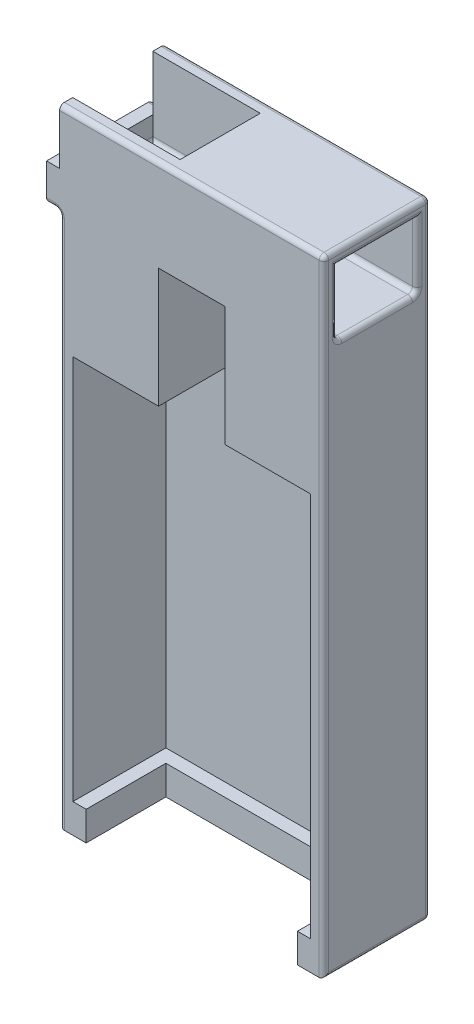
SolidWorks part; units mm, degrees
ref_plane "Front Plane" through (0, 0, 0) normal (0, 0, 1) x (1, 0, 0)
ref_plane "Top Plane" through (0, 0, 0) normal (0, 1, 0) x (1, 0, 0)
ref_plane "Right Plane" through (0, 0, 0) normal (1, 0, 0) x (0, 0, -1)
sketch "Sketch1" plane through (0, 0, 0) normal (0, 1, 0) x (1, 0, 0)
  line L0 (-22.733, -7.62) -> (-22.733, -10.16)
  line L1 (-25.273, -10.16) -> (25.273, -10.16)
  line L2 (-25.273, -10.16) -> (-25.273, 10.16)
  line L3 (-25.273, 10.16) -> (25.273, 10.16)
  line L4 (25.273, -10.16) -> (25.273, 10.16)
  line L5 (-25.273, -10.16) -> (25.273, 10.16) construction
  line L6 (-25.273, 10.16) -> (25.273, -10.16) construction
  line L7 (-22.733, -7.62) -> (22.733, -7.62)
  line L8 (-22.733, -7.62) -> (-22.733, 7.62)
  line L9 (-22.733, 7.62) -> (22.733, 7.62)
  line L10 (22.733, -7.62) -> (22.733, 7.62)
  line L11 (-22.733, -7.62) -> (22.733, 7.62) construction
  line L12 (-22.733, 7.62) -> (22.733, -7.62) construction
  line L13 (22.733, -7.62) -> (22.733, -10.16)
  line L14 (-22.733, -7.62) -> (-25.273, -7.62) construction
  line L15 (-20.193, -5.08) -> (-20.193, -10.16)
  line L17 (-20.193, -5.08) -> (-20.193, 5.08)
  line L18 (-20.193, 5.08) -> (20.193, 5.08)
  line L19 (20.193, -5.08) -> (20.193, 5.08)
  line L20 (-20.193, -5.08) -> (20.193, 5.08) construction
  line L21 (-20.193, 5.08) -> (20.193, -5.08) construction
  line L22 (20.193, -5.08) -> (20.193, -10.16)
  line L23 (-20.193, -5.08) -> (-22.733, -5.08) construction
  line L24 (-20.193, 5.08) -> (-20.193, 7.62) construction
  line L25 (0, -3.175) -> (0, 3.81) construction
  line L26 (-6.35, -3.175) -> (-6.35, 3.81)
  line L27 (6.35, -3.175) -> (6.35, 3.81)
  line L28 (-6.35, -3.175) -> (-6.35, -10.16)
  line L29 (6.35, -3.175) -> (6.35, -10.16)
  arc A1 (6.35, 3.81) -> (-6.35, 3.81) centre (0, 3.81) ccw
  point P0 (0, 0)
  point P6 (0, 0)
  point P11 (0, 0)
  dimension "D4" = 6.35
  dimension "D1" = 15.24
  dimension "D2" = 2.54
  dimension "D3" = 45.466
extrude "Boss-Extrude3" add sketch "Sketch1" along normal blind 5.588 contours A1 L3 L2 L1 L0 L8 L9 | A1 L9 L10 L13 L1 L4 L3 | L9 A1 | A1 L9 L8 L7 L15 L17 L18 | L15 L7 L0 L1 | L18 A1 L9 | A1 L18 L19 L22 L7 L10 L9 | L7 L22 L1 L13 region at (-21.463, 0, 8.89) region at (-22.4998, 0, 0) region at (-23.0573, 0, 8.89) region at (0, 0, -8.6557) region at (0, 0, -6.3086) region at (2.9848, 0, -9.7797) region at (13.9065, 0, -7.3868) region at (21.463, 0, 8.89)
extrude "Boss-Extrude4" add sketch "Sketch1<7>" along normal blind 73.66 from surface contours A1 L3 L2 L1 L0 L8 L9 | A1 L9 L10 L13 L1 L4 L3 | L9 A1 region at (-23.0573, 0, 8.89) region at (0, 0, -8.6557) region at (2.9848, 0, -9.7797) starting at face at (0, 5.588, 1.27)
sketch "Sketch1<7>" plane through (0, 0, 0) normal (0, 1, 0) x (1, 0, 0) same geometry as "Sketch1"
extrude "Boss-Extrude6" add sketch "Sketch1<8>" along normal blind 22.86 from surface contours A1 L3 L2 L1 L0 L8 L9 | A1 L9 L8 L7 L15 L17 L18 | A1 L18 L17 L15 L7 L28 L26 | L15 L7 L0 L1 | L28 L7 L15 L1 | A1 L9 L10 L13 L1 L4 L3 | A1 L18 L19 L22 L7 L10 L9 | A1 L27 L29 L7 L22 L19 L18 | L7 L29 L1 L22 | L7 L22 L1 L13 | L9 A1 region at (-21.463, 0, 8.89) region at (-22.4998, 0, 0) region at (-23.0573, 0, 8.89) region at (-13.2694, 0, 1.2681) region at (-13.2715, 0, 8.89) region at (0, 0, -8.6557) region at (13.2694, 0, 1.2681) region at (13.2715, 0, 8.89) region at (2.9848, 0, -9.7797) region at (13.9065, 0, -7.3868) region at (21.463, 0, 8.89) starting at face at (0, 79.248, 0.635)
sketch "Sketch1<8>" plane through (0, 0, 0) normal (0, 1, 0) x (1, 0, 0) same geometry as "Sketch1"
extrude "Boss-Extrude7" add sketch "Sketch1<9>" along normal blind 2.54 from surface contours L27 A1 L18 L26 L28 L7 L29 | L29 L7 L28 L1 | L18 A1 L9 | A1 L3 L2 L1 L0 L8 L9 | L15 L7 L0 L1 | A1 L9 L8 L7 L15 L17 L18 | L28 L7 L15 L1 | A1 L18 L17 L15 L7 L28 L26 | L9 A1 | A1 L18 L19 L22 L7 L10 L9 | A1 L9 L10 L13 L1 L4 L3 | A1 L27 L29 L7 L22 L19 L18 | L7 L29 L1 L22 | L7 L22 L1 L13 | L3 L4 L1 L2 region at (-21.463, 0, 8.89) region at (-22.4998, 0, 0) region at (-23.0573, 0, 8.89) region at (-13.2694, 0, 1.2681) region at (-13.2715, 0, 8.89) region at (0, 0, 1.274) region at (0, 0, 8.89) region at (0, 0, -8.6557) region at (0, 0, -6.3086) region at (13.2694, 0, 1.2681) region at (13.2715, 0, 8.89) region at (2.9848, 0, -9.7797) region at (13.9065, 0, -7.3868) region at (21.463, 0, 8.89) starting at face at (0, 102.108, -0.2746)
sketch "Sketch1<9>" plane through (0, 0, 0) normal (0, 1, 0) x (1, 0, 0) same geometry as "Sketch1"
sketch "Sketch2" plane through (0, 104.648, 0) normal (0, 1, 0) x (1, 0, 0)
  line L0 (-25.273, 10.16) -> (-25.273, 7.66)
  line L1 (-25.273, 10.16) -> (-25.273, -10.16) construction
  line L2 (-25.273, 7.66) -> (25.273, 7.66)
  line L3 (25.273, 10.16) -> (25.273, -10.16) construction
  line L4 (25.273, 7.66) -> (25.273, 10.16)
  line L5 (25.273, 10.16) -> (-25.273, 10.16)
  line L6 (-25.273, -10.16) -> (-25.273, -7.66)
  line L7 (-25.273, -7.66) -> (25.273, -7.66)
  line L8 (25.273, -7.66) -> (25.273, -10.16)
  line L9 (25.273, -10.16) -> (-25.273, -10.16)
  dimension "D1" = 2.5
  dimension "D2" = 2.5
extrude "Boss-Extrude8" add sketch "Sketch2" along normal blind 15
sketch "Sketch3" plane through (0, 0, -7.66) normal (0, 0, 1) x (1, 0, 0)
  line L0 (25.273, 119.648) -> (-4.727, 119.648)
  line L1 (-25.273, 119.648) -> (25.273, 119.648) construction
  line L2 (-4.727, 119.648) -> (-4.727, 117.148)
  line L3 (-4.727, 117.148) -> (25.273, 117.148)
  line L4 (25.273, 119.648) -> (25.273, 104.648) construction
  line L5 (25.273, 117.148) -> (25.273, 119.648)
  dimension "D1" = 30
  dimension "D2" = 2.5
extrude "Boss-Extrude9" add sketch "Sketch3" along normal up to next
sketch "Sketch4" plane through (-25.273, 0, 0) normal (-1, 0, 0) x (0, 0, 1)
  line L0 (-10.16, 119.648) -> (-10.16, 0) construction
  line L1 (-10.16, 109.148) -> (10.16, 109.148)
  line L2 (-10.16, 109.148) -> (-10.16, 102.148)
  line L3 (-10.16, 102.148) -> (10.16, 102.148)
  line L4 (10.16, 109.148) -> (10.16, 102.148)
  line L5 (10.16, 119.648) -> (10.16, 0) construction
  line L6 (-7.66, 104.648) -> (7.66, 104.648) construction
  dimension "D1" = 7
  dimension "D2" = 2.5
extrude "Boss-Extrude10" add sketch "Sketch4" along normal blind 2.5
fillet "Fillet1" radius 0.905 23 edges at (0, 0, -10.16) (-25.273, 51.074, -10.16) (-25.273, 51.074, 10.16) (-25.273, 0, 0) (25.273, 59.824, 10.16) (25.273, 59.824, -10.16) (25.273, 0, 0) (25.273, 104.648, 0) (-26.523, 102.148, 10.16) (0, 119.648, -10.16) (-25.273, 114.398, -10.16) (-26.523, 109.148, -10.16) (-27.773, 105.648, -10.16) (-26.523, 102.148, -10.16) (-25.273, 102.148, 0) (25.273, 119.648, 0) (25.273, 110.898, -7.66) (25.273, 117.148, 0) (25.273, 110.898, 7.66) (0, 104.648, 7.66) (-25.273, 104.648, 0) (0, 104.648, -7.66) (0, 119.648, 10.16)
